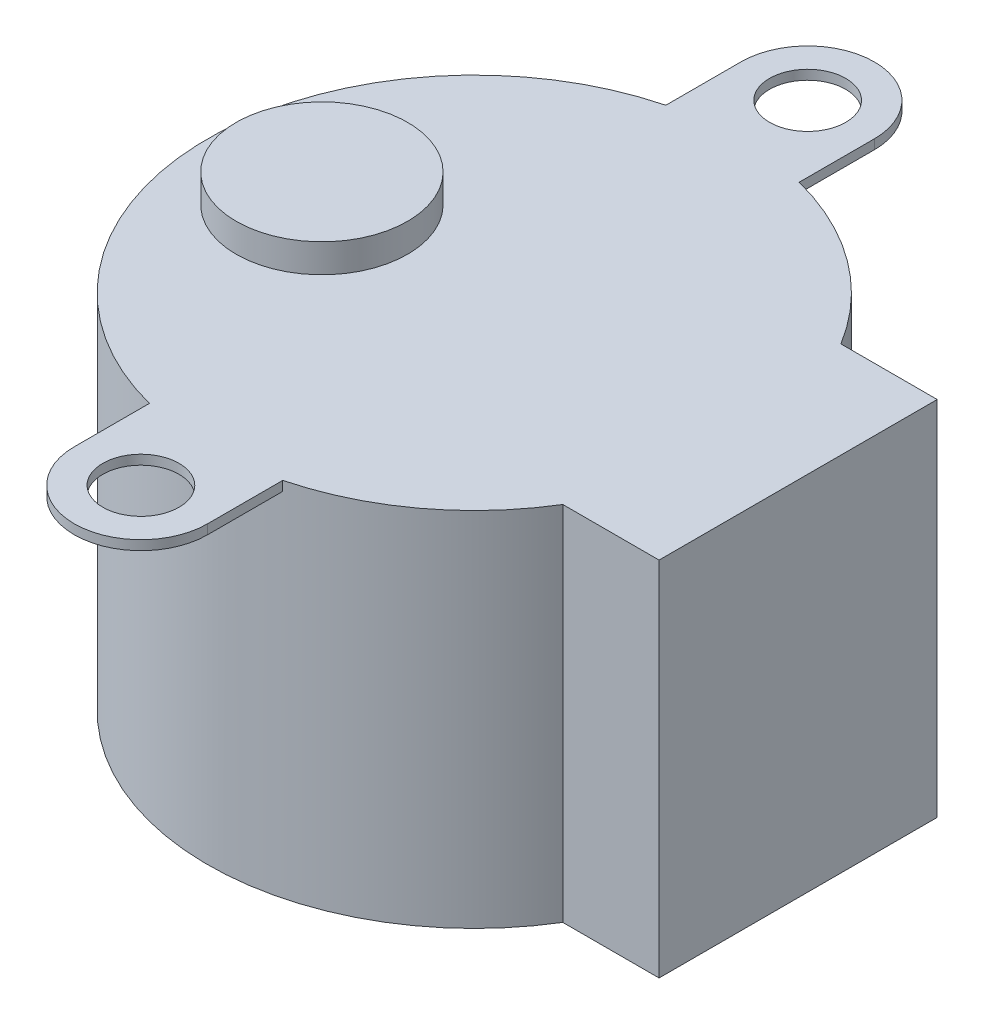
SolidWorks part; units mm, degrees
ref_plane "Front Plane" through (0, 0, 0) normal (0, 0, 1) x (1, 0, 0)
ref_plane "Top Plane" through (0, 0, 0) normal (0, 1, 0) x (1, 0, 0)
ref_plane "Right Plane" through (0, 0, 0) normal (1, 0, 0) x (0, 0, -1)
sketch "Sketch1" plane through (0, 0, 0) normal (0, 1, 0) x (1, 0, 0)
  line L1 (11.9461, 7.3) -> (17, 7.3)
  line L3 (11.9461, -7.3) -> (17, -7.3)
  line L4 (17, 7.3) -> (17, -7.3)
  arc A0 (11.9461, 7.3) -> (11.9461, -7.3) centre (0, 0) ccw
  dimension "D1" = 28
  dimension "D2" = 17
  dimension "D3" = 14.6
extrude "Boss-Extrude1" add sketch "Sketch1" along normal blind 19
sketch "Sketch3" plane through (0, 19, 0) normal (0, 1, 0) x (1, 0, 0)
  line L0 (0, 17.5) -> (0, -17.5) construction
  line L1 (3.5, 17.5) -> (3.5, -17.5)
  line L2 (-3.5, 17.5) -> (-3.5, -17.5)
  arc A0 (3.5, 17.5) -> (-3.5, 17.5) centre (0, 17.5) ccw
  arc A1 (-3.5, -17.5) -> (3.5, -17.5) centre (0, -17.5) ccw
  circle A2 centre (0, -17.5) radius 2
  circle A3 centre (0, 17.5) radius 2
  point P2 (0, 0)
  dimension "D2" = 4
  dimension "D1" = 7
  dimension "D3" = 35
extrude "Boss-Extrude2" add sketch "Sketch3" against normal blind 0.5
sketch "Sketch4" plane through (0, 19, 0) normal (0, 1, 0) x (1, 0, 0)
  circle A0 centre (-8, 0) radius 4.5
  dimension "D2" = 9
  dimension "D1" = 8
extrude "Boss-Extrude3" add sketch "Sketch4" along normal blind 1.5
